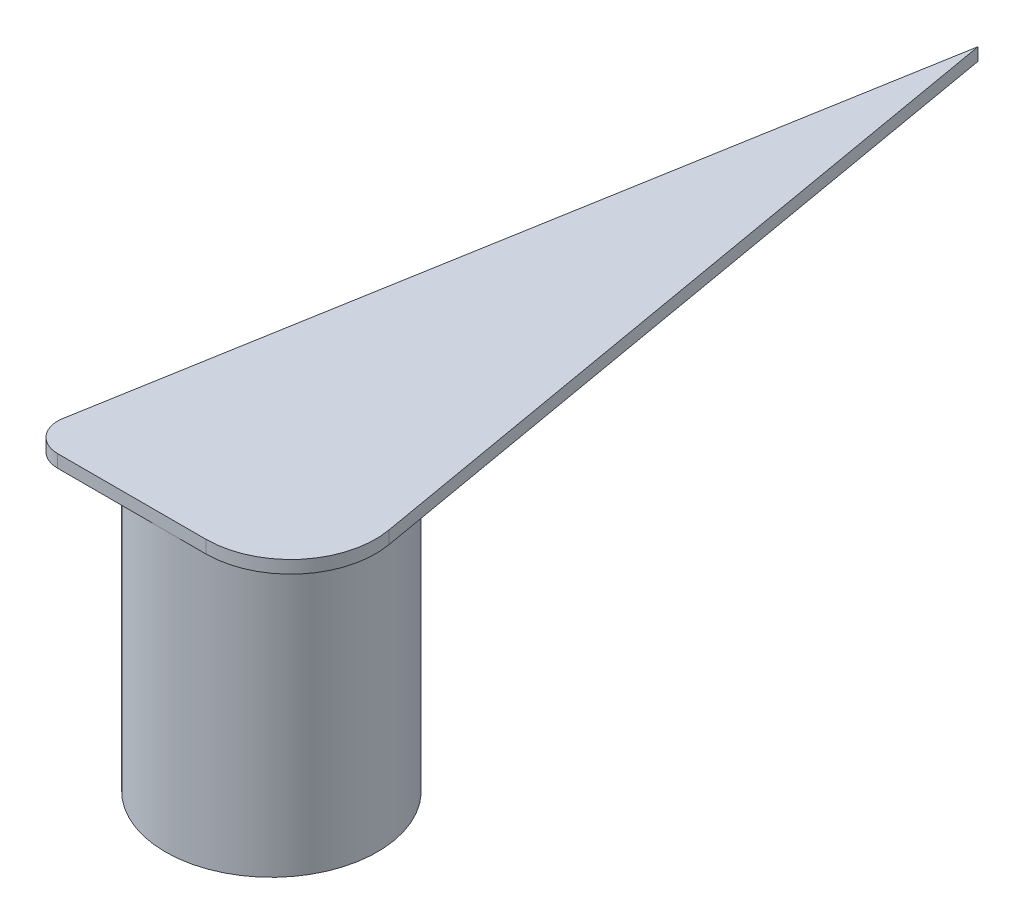
SolidWorks part; units mm, degrees
material "Plain Carbon Steel"
ref_plane "Front Plane" through (0, 0, 0) normal (0, 0, 1) x (1, 0, 0)
ref_plane "Top Plane" through (0, 0, 0) normal (0, 1, 0) x (1, 0, 0)
ref_plane "Right Plane" through (0, 0, 0) normal (1, 0, 0) x (0, 0, -1)
sketch "Sketch1" plane through (0, 0, 0) normal (0, 1, 0) x (1, 0, 0)
  circle A0 centre (0, 0) radius 7.5
  dimension "D1" = 15
extrude "Boss-Extrude1" add sketch "Sketch1" along normal blind 1.8
extrude "Boss-Extrude2" add sketch "Sketch1<3>" against normal blind 18.8
sketch "Sketch1<3>" plane through (0, 0, 0) normal (0, 1, 0) x (1, 0, 0) same geometry as "Sketch1"
sketch "Sketch3" plane through (0, 1.8, 0) normal (0, 1, 0) x (1, 0, 0)
  line L0 (0, 50) -> (-10, -7.5)
  line L1 (-10, -7.5) -> (10, -7.5)
  line L2 (10, -7.5) -> (0, 50)
  line L4 (0, 50) -> (0, 0) construction
  circle A0 centre (0, 0) radius 7.5 construction
  point P8 (6.9251, -4.9211)
  point P9 (8.9065, -1.2126)
  dimension "D1" = 50
  dimension "D2" = 20
extrude "Boss-Extrude3" add sketch "Sketch3" against normal blind 0.9
fillet "Fillet1" radius 6 1 edges at (10, 1.35, 7.5)
fillet "Fillet2" radius 2 1 edges at (-10, 1.35, 7.5)
